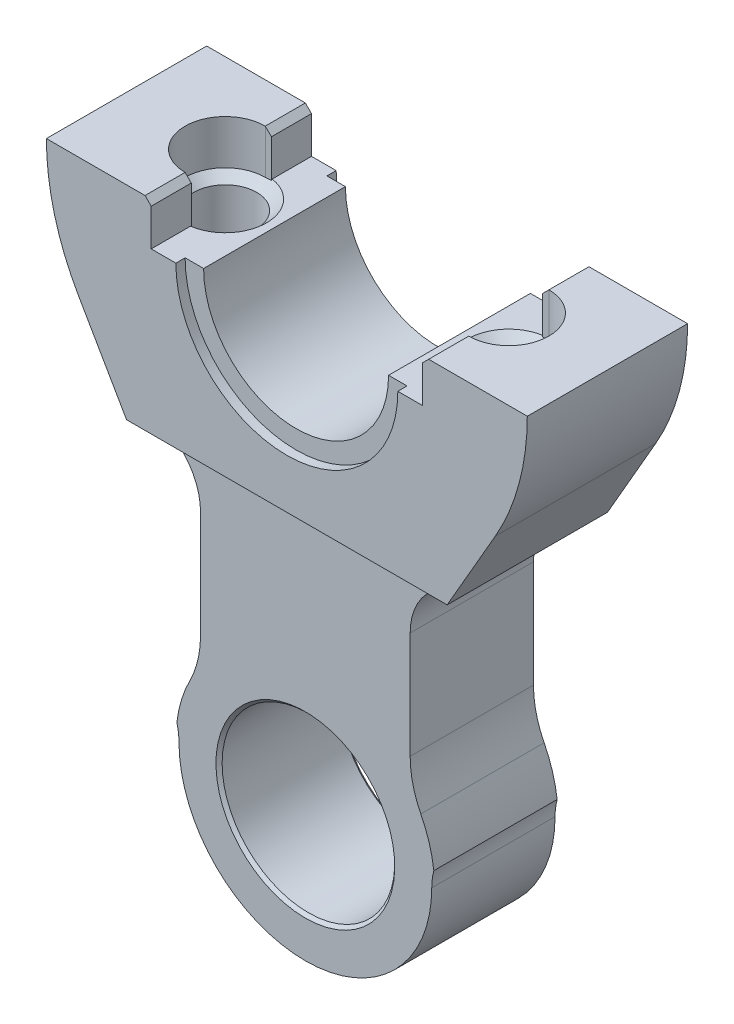
SolidWorks part; units mm, degrees
material "Простая углеродистая сталь"
ref_plane "Спереди" through (0, 0, 0) normal (0, 0, 1) x (1, 0, 0)
ref_plane "Сверху" through (0, 0, 0) normal (0, 1, 0) x (1, 0, 0)
ref_plane "Справа" through (0, 0, 0) normal (1, 0, 0) x (0, 0, -1)
sketch "Эскиз1" plane through (0, 0, 0) normal (0, 0, 1) x (1, 0, 0)
  line L0 (0, -128.6383) -> (0, 22.4317) construction
  line L1 (33.7958, -19.4639) -> (26, -33)
  line L2 (26, -33) -> (17, -33)
  line L3 (17, -33) -> (17, -60.2668)
  line L4 (-17, -33) -> (-17, -60.2668)
  line L5 (-26, -33) -> (-17, -33)
  line L6 (-33.7958, -19.4639) -> (-26, -33)
  line L7 (39, 0) -> (22, 0)
  line L8 (-75.2542, 0) -> (75.2542, 0) construction
  line L9 (22, 0) -> (22, -7)
  line L10 (-22, -7) -> (-15, -7)
  line L11 (22, -7) -> (15, -7)
  line L12 (-22, -7) -> (-22, 0)
  line L13 (-22, 0) -> (-39, 0)
  arc A0 (-39, 0) -> (-33.7958, -19.4639) centre (0, 0) ccw
  arc A1 (17, -60.2668) -> (18.7297, -67.5028) centre (33, -60.2668) ccw
  arc A2 (18.7297, -67.5028) -> (20.8402, -74.414) centre (0, -77) cw
  arc A3 (20.8402, -74.414) -> (20.5, -77) centre (30.5, -77) ccw
  arc A4 (20.5, -77) -> (-20.5, -77) centre (0, -77) cw
  arc A5 (-20.8402, -74.414) -> (-20.5, -77) centre (-30.5, -77) cw
  arc A6 (33.7958, -19.4639) -> (39, 0) centre (0, 0) ccw
  arc A7 (-18.7297, -67.5028) -> (-20.8402, -74.414) centre (0, -77) ccw
  arc A8 (-17, -60.2668) -> (-18.7297, -67.5028) centre (-33, -60.2668) cw
  arc A9 (15, -7) -> (-15, -7) centre (0, -7) cw
  circle A10 centre (0, -77) radius 14
  point P28 (0, 0)
  dimension "D5" = 16
  dimension "D6" = 10
  dimension "D7" = 21
  dimension "D8" = 20.5
  dimension "D9" = 44
  dimension "D10" = 15
  dimension "D13" = 28
  dimension "D14" = 39
  dimension "D2" = 33
  dimension "D3" = 52
  dimension "D4" = 34
  dimension "D11" = 7
  dimension "D12" = 70
extrude "Бобышка-Вытянуть1" add sketch "Эскиз1" along normal mid plane 26
fillet "Скругление1" radius 10 2 edges at (-17, -33, 0) (17, -33, 0)
sketch "Эскиз2" plane through (0, 0, 0) normal (1, 0, 0) x (0, 0, -1)
  line L0 (0, 17.4918) -> (0, -107.1669) construction
  line L1 (13, 0) -> (-13, 0)
  line L2 (-13, -97.5) -> (13, -97.5) construction
  line L3 (10, -97.5) -> (10, -34.6)
  line L4 (11.6, -33) -> (13, -33)
  line L5 (13, -33) -> (13, -19.4639) construction
  line L6 (13, -33) -> (13, 0)
  line L7 (-13, 0) -> (-13, -33)
  line L8 (-11.6, -33) -> (-13, -33)
  line L9 (-10, -97.5) -> (-10, -34.6)
  line L10 (-10, -97.5) -> (10, -97.5)
  arc A0 (11.6, -33) -> (10, -34.6) centre (11.6, -34.6) ccw
  arc A1 (-11.6, -33) -> (-10, -34.6) centre (-11.6, -34.6) cw
  dimension "D1" = 1.6
  dimension "D3" = 20
extrude "Вырез-Вытянуть1" cut sketch "Эскиз2" against normal through all and the other way through all flip side to cut
sketch "Эскиз3" plane through (0, 0, 0) normal (0, 1, 0) x (1, 0, 0)
  line L0 (-43.1962, 0) -> (42.0701, 0) construction
  line L1 (0, -22.5634) -> (0, 18.8632) construction
  line L2 (23, 6.5) -> (22, 6.5)
  line L3 (22, -13) -> (22, 13) construction
  line L4 (23, -6.5) -> (22, -6.5)
  line L5 (22, 6.5) -> (22, -6.5)
  line L6 (-22, 6.5) -> (-22, -6.5)
  line L7 (-23, -6.5) -> (-22, -6.5)
  line L8 (-23, 6.5) -> (-22, 6.5)
  arc A0 (23, -6.5) -> (23, 6.5) centre (23, 0) ccw
  arc A1 (-23, -6.5) -> (-23, 6.5) centre (-23, 0) cw
  dimension "D1" = 6.5
  dimension "D2" = 46
extrude "Вырез-Вытянуть2" cut sketch "Эскиз3" against normal up to surface (7 mm away) up to face at (-18.5, -7, 0)
chamfer "Фаска1" distance 1 angle 45 4 edges at (22, 0, -9.75) (22, 0, 9.75) (-22, 0, 9.75) (-22, 0, -9.75)
chamfer "Фаска2" distance 0.5 angle 45 2 edges at (-14, -77, -10) (0, -91, 10)
sketch "Эскиз4" plane through (0, 0, 13) normal (0, 0, 1) x (1, 0, 0)
  line L0 (0, 3.7548) -> (0, -38.5353) construction
  circle A0 centre (0, -7) radius 18
  arc A3 (-15, -7) -> (15, -7) centre (0, -7) ccw construction
  arc A4 (-15, -7) -> (15, -7) centre (0, -7) ccw construction
  dimension "D1" = 36
extrude "Вырез-Вытянуть3" cut sketch "Эскиз4" against normal blind 1.5
mirror "Зеркальное отражение1" about plane through (0, 0, 0) normal (0, 0, 1) of "Вырез-Вытянуть3"
hole_wizard "Отверстие обработанное метчиком M121" positions "Эскиз7" profile "Эскиз6" tap size "M12" standard "Iso"
sketch "Эскиз7" plane through (0, -7, 0) normal (0, 1, 0) x (1, 0, 0)
  point P0 (-23, 0)
  point P2 (23, 0)
sketch "Эскиз6" plane through (-23, -7, 0) normal (1, 0, 0) x (0, 0, 1)
  line L0 (0, 0) -> (0, 19.9445)
  line L1 (0, 19.9445) -> (5.1, 17)
  line L2 (5.1, 17) -> (5.1, 0)
  line L5 (5.1, 0) -> (0, 0)
  line L10 (0, 19.9445) -> (-5.1, 17) construction
  line L11 (0, -6.35) -> (0, 107.95) construction
  dimension "Диаметр сверла" = 10.2
  dimension "Глубина сверла" = 17
  dimension "Угол заточки сверла" = 120
cosmetic thread "Отверстие резьбы1" parameters "D1"=12, "D2"=12
cosmetic thread "Отверстие резьбы2" parameters "D1"=12, "D2"=12
chamfer "Фаска3" distance 1.6 angle 45 2 edges at (23, -7, 5.1) (-23, -7, 5.1)
